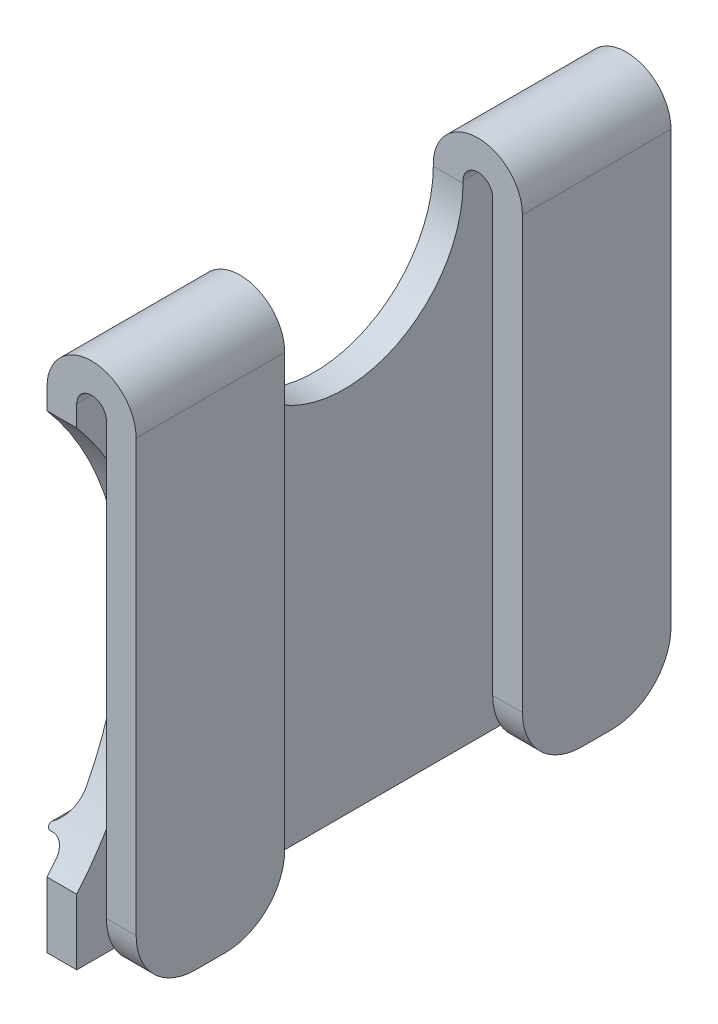
SolidWorks part; units mm, degrees
ref_plane "前视基准面" through (0, 0, 0) normal (0, 0, 1) x (1, 0, 0)
ref_plane "上视基准面" through (0, 0, 0) normal (0, 1, 0) x (1, 0, 0)
ref_plane "右视基准面" through (0, 0, 0) normal (1, 0, 0) x (0, 0, -1)
other "Configuration Table"
sketch "草图1" plane through (0, 0, 0) normal (1, 0, 0) x (0, 0, -1)
  line L1 (-45, -45) -> (45, -45)
  line L2 (-45, -45) -> (-45, 45)
  line L3 (-45, 45) -> (45, 45)
  line L4 (45, -45) -> (45, 45)
  line L5 (-45, -45) -> (45, 45) construction
  line L6 (-45, 45) -> (45, -45) construction
  point P0 (0, 0)
  dimension "D1" = 90
  dimension "D2" = 90
extrude "凸台-拉伸1" add sketch "草图1" along normal blind 15
sketch "草图2" plane through (0, 0, 45) normal (0, 0, 1) x (1, 0, 0)
  line L0 (5, -45) -> (5, 37.5)
  line L1 (15, -45) -> (0, -45) construction
  line L3 (10, 37.5) -> (10, -45)
  line L4 (10, -45) -> (5, -45)
  line L5 (0, 45) -> (0, -45) construction
  line L6 (15, 45) -> (15, -45) construction
  line L8 (15, 45) -> (0, 45) construction
  line L9 (0, 37.5) -> (0, 45)
  line L10 (0, 45) -> (7.5, 45)
  line L11 (7.5, 45) -> (15, 45)
  line L12 (15, 45) -> (15, 37.5)
  line L13 (0, 37.5) -> (15, 37.5) construction
  arc A0 (10, 37.5) -> (5, 37.5) centre (7.5, 37.5) ccw
  arc A1 (0, 37.5) -> (15, 37.5) centre (7.5, 37.5) cw
  line M6 (0, 45) -> (0, -45)
  line M7 (0, -45) -> (15, -45)
  line M8 (15, -45) -> (15, 45)
  line M9 (15, 45) -> (0, 45)
  dimension "D3" = 7.5
  dimension "D1" = 5
  dimension "D2" = 5
extrude "切除-拉伸1" cut sketch "草图2" against normal through all contours A1 M6 M9 | A1 M9 M8 | A0 L13 | L13 L0 L3 M7 region at (7.5, -3.75, 45) region at (7.5, 38.561, 45) region at (1.6753, 43.3247, 45) region at (13.3247, 43.3247, 45)
sketch "草图3" plane through (15, 0, 0) normal (1, 0, 0) x (0, 0, -1)
  line L0 (45, 45) -> (-45, 45) construction
  line L1 (-20, -45) -> (20, -45)
  line L2 (-20, -45) -> (-20, 45)
  line L3 (-20, 45) -> (20, 45)
  line L4 (20, -45) -> (20, 45)
  line L5 (-20, -45) -> (20, 45) construction
  line L6 (-20, 45) -> (20, -45) construction
  line L7 (-45, 37.5) -> (-45, -45) construction
  point P0 (0, 0)
  dimension "D1" = 25
extrude "切除-拉伸2" cut sketch "草图3" against normal up to surface (10 mm away) up to face at (5, -3.75, 0)
fillet "圆角1" radius 10 4 edges at (12.5, -45, -45) (12.5, -45, -20) (12.5, -45, 20) (12.5, -45, 45)
sketch "草图4" plane through (5, 0, 0) normal (1, 0, 0) x (0, 0, -1)
  line L0 (-20, 44.5711) -> (-20, 37.1045)
  line L1 (-20, 37.5) -> (-20, -35) construction
  line L2 (-20, 44.5711) -> (20, 44.5711)
  line L3 (20, 44.5711) -> (20, 37.1045)
  line L4 (20, -35) -> (20, 37.5) construction
  line L5 (20, 37.1045) -> (-20, 37.1045) construction
  arc A0 (20, 37.1045) -> (-20, 37.1045) centre (0, 37.1045) cw
extrude "切除-拉伸3" cut sketch "草图4" against normal through all
sketch "草图7" plane through (0, 0, 0) normal (0, 0, 1) x (1, 0, 0)
  line L1 (0, -30) -> (-6, -30)
  line L4 (0, -45) -> (-6, -45)
  line L5 (-6, -30) -> (-6, -45) construction
  line L6 (0, -30) -> (0, -45)
  circle A0 centre (-6, -37.5) radius 5
  arc A1 (-6, -45) -> (-6, -30) centre (-6, -37.5) cw
  point P2 (0, 0)
  point P6 (0, 0)
  point P10 (0, 0)
  dimension "D1" = 10
  dimension "D2" = 7.5
  dimension "D3" = 6
extrude "凸台-拉伸4" add sketch "草图7" along normal blind 15 and the other way blind 15
sketch "草图9" plane through (0, 0, 0) normal (0, 0, 1) x (1, 0, 0)
  line L0 (0, -24) -> (-6, -24) construction
  line L1 (-6, -24) -> (-6, -30) construction
  line L3 (0, -24) -> (0, -30)
  line L4 (0, -30) -> (-6, -30)
  arc A0 (-6, -30) -> (0, -24) centre (-6, -24) ccw
  arc A1 (-6, -30) -> (-6, -45) centre (-6, -37.5) ccw construction
  point P3 (0, 0)
extrude "凸台-拉伸5" add sketch "草图9" along normal blind 45 and the other way blind 45
sketch "草图6" plane through (0, 0, 0) normal (-1, 0, 0) x (0, 0, 1)
  line L0 (45, 37.5) -> (45, -24) construction
  line L1 (32.5, -955) -> (32.5, 49045) construction
  line L2 (45, 45) -> (20, 45) construction
  line L3 (0, -1000) -> (0, 49000) construction
  line L4 (-1000.7858, 0) -> (48999.2142, 0) construction
  line L5 (45, 33.9698) -> (45, -33.9698)
  line L6 (-45, 33.9698) -> (-45, -33.9698)
  arc A0 (45, 33.9698) -> (45, -33.9698) centre (84.9079, 0) ccw
  arc A1 (-45, 33.9698) -> (-45, -33.9698) centre (-84.9079, 0) cw
  point P10 (32.5, 45)
extrude "切除-拉伸4" cut sketch "草图6" against normal up to surface (10 mm away) and the other way blind 15 up to face at (10, -14.857, 32.5)
fillet "圆角2" radius 0.5 2 edges at (-6, -30, -28.468) (-6, -30, 28.468)
fillet "圆角3" radius 2 2 edges at (0, -30, -28.468) (0, -30, 28.468)
